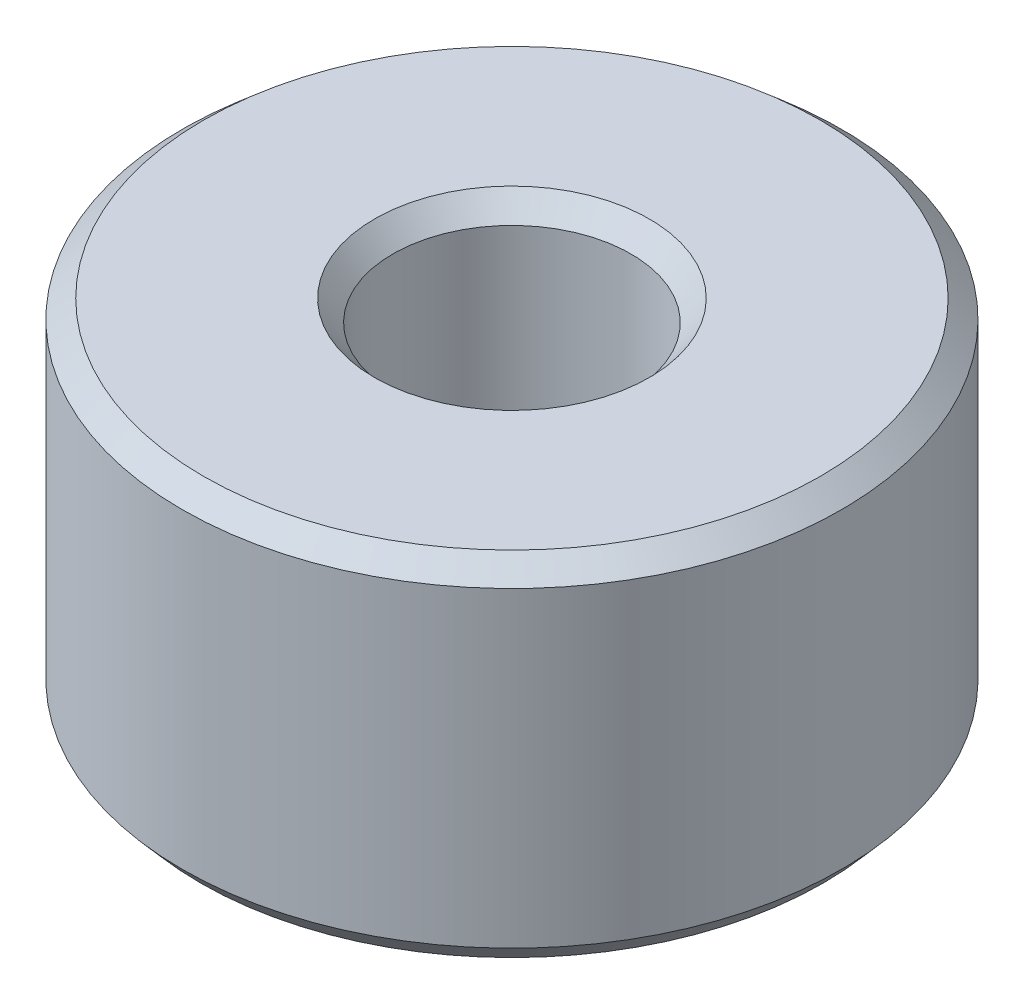
SolidWorks part; units mm, degrees
ref_plane "Front Plane" through (0, 0, 0) normal (0, 0, 1) x (1, 0, 0)
ref_plane "Top Plane" through (0, 0, 0) normal (0, 1, 0) x (1, 0, 0)
ref_plane "Right Plane" through (0, 0, 0) normal (1, 0, 0) x (0, 0, -1)
sketch "Sketch1" plane through (0, 0, 0) normal (0, 1, 0) x (1, 0, 0)
  circle A0 centre (0, 0) radius 17.5
  dimension "SLEEVE_OD" = 35
extrude "Boss-Extrude1" add sketch "Sketch1" along normal blind 18.636
sketch "Sketch2" plane through (0, 0, 0) normal (0, 1, 0) x (1, 0, 0)
  circle A0 centre (0, 0) radius 6.3223
  dimension "BORE_D" = 12.6446
extrude "Cut-Extrude1" cut sketch "Sketch2" along normal through all
chamfer "Chamfer1" distance 0.9748 angle 48.989 4 edges at (0, 18.636, 6.3223) (0, 0, 6.3223) (0, 0, 17.5) (0, 18.636, 17.5) first distance on face at (0, 18.636, 6.3223) first distance on face at (0, 0, 6.3223) first distance on face at (0, 18.636, 17.5)
